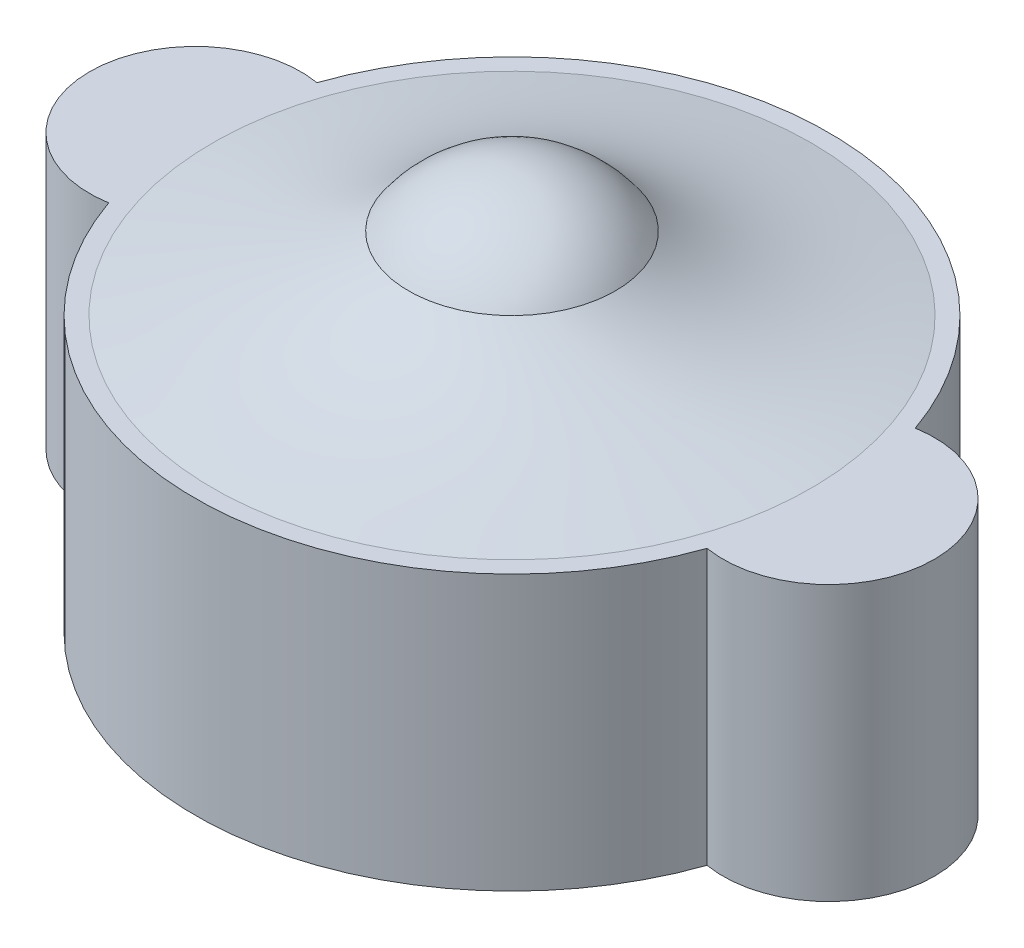
SolidWorks part; units mm, degrees
ref_plane "Front Plane" through (0, 0, 0) normal (0, 0, 1) x (1, 0, 0)
ref_plane "Top Plane" through (0, 0, 0) normal (0, 1, 0) x (1, 0, 0)
ref_plane "Right Plane" through (0, 0, 0) normal (1, 0, 0) x (0, 0, -1)
sketch "Sketch1" plane through (0, 0, 0) normal (0, 1, 0) x (1, 0, 0)
  circle A0 centre (0, 0) radius 19.05
  arc A1 (-17.9917, 6.2612) -> (-17.9917, -6.2612) centre (-19.05, 0) ccw
  arc A2 (17.9917, -6.2612) -> (17.9917, 6.2612) centre (19.05, 0) ccw
  dimension "D1" = 38.1
  dimension "D2" = 12.7
extrude "Boss-Extrude1" add sketch "Sketch1" along normal blind 16.51 contours A0 | A0 A1 | A0 A2 region at (0, 0, 0) region at (21.5454, 0, 0) region at (-21.5454, 0, 0)
sketch "Sketch2" plane through (0, 16.51, 0) normal (0, 1, 0) x (1, 0, 0)
  line L0 (0, 0) -> (25.4, 0)
  line L1 (0, 0) -> (-13.335, 0)
  arc A0 (-7.62, 0) -> (7.62, 0) centre (0, 0) ccw
  arc A1 (-13.335, 0) -> (13.335, 0) centre (0, 0) ccw
  arc A2 (17.9917, -6.2612) -> (17.9917, 6.2612) centre (19.05, 0) ccw construction
  dimension "D1" = 15.24
  dimension "D2" = 26.67
revolve "Cut-Revolve4" cut sketch "Sketch2" angle 360 about L0 region at (0, 16.51, 3.234) region at (10.4775, 16.51, 0.2982)
revolve "Revolve1" add sketch "Sketch2<7>" angle 360 about L0 region at (0, 16.51, 3.234)
sketch "Sketch2<7>" plane through (0, 16.51, 0) normal (0, 1, 0) x (1, 0, 0) same geometry as "Sketch2"
sketch "Sketch3" plane through (0, 0, 0) normal (0, 0, 1) x (1, 0, 0)
  line L1 (17.9917, 16.51) -> (-17.9917, 16.51) construction
  line L2 (17.9917, 16.51) -> (-17.9917, 16.51)
  line L3 (0, 16.51) -> (0, 24.0784)
  line L4 (-7.62, 16.51) -> (-17.9917, 16.51)
  circle A0 centre (0, 16.51) radius 7.62 construction
  spline S0 degree 3 poles (-17.9917, 16.51) (-13.9499, 17.4015) (-9.5623, 18.2458) (-6.2256, 20.9039) knots 0 0 0 0 1 1 1 1
  spline S1 degree 2 poles (-6.2256, 20.9039) (-7.6007, 18.9308) (-7.62, 16.51) knots 0 0 0 1 1 1
revolve "Revolve2" add sketch "Sketch3" angle 360 about L3 region at (-10.5059, 17.6783, 0)
